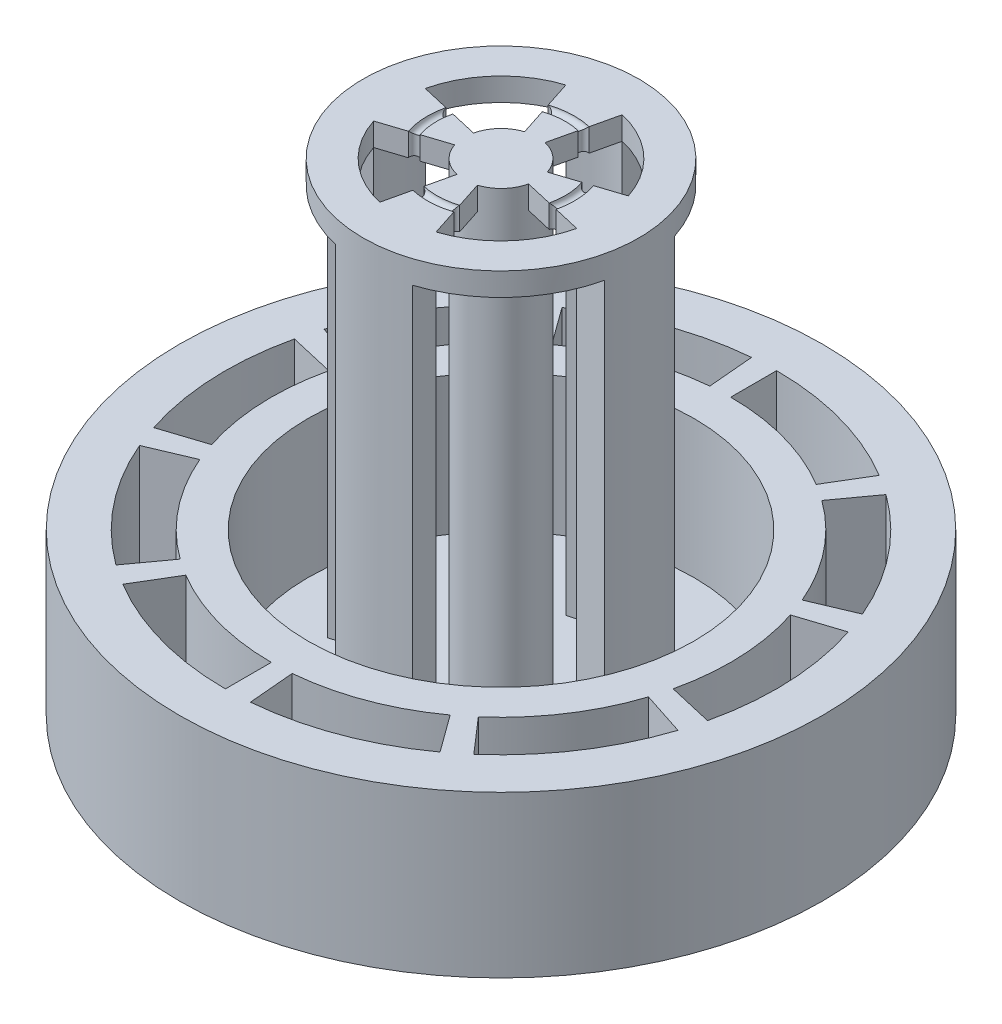
SolidWorks part; units mm, degrees
ref_plane "Front Plane" through (0, 0, 0) normal (0, 0, 1) x (1, 0, 0)
ref_plane "Top Plane" through (0, 0, 0) normal (0, 1, 0) x (1, 0, 0)
ref_plane "Right Plane" through (0, 0, 0) normal (1, 0, 0) x (0, 0, -1)
sketch "Sketch1" plane through (0, 0, 0) normal (0, 1, 0) x (1, 0, 0)
  circle A0 centre (0, 0) radius 70
extrude "Boss-Extrude1" add sketch "Sketch1" along normal blind 5
sketch "Sketch2" plane through (0, 0, 0) normal (0, 1, 0) x (1, 0, 0)
  line L0 (-17.6336, -24.2705) -> (-35.2671, -48.541)
  line L1 (-15.4511, -25.715) -> (-30.9023, -51.43)
  line L2 (-7.6085, -2.4721) -> (-57.0634, -18.541)
  line L3 (-27.6151, -11.7219) -> (-55.2303, -23.4439)
  line L4 (-28.5317, 9.2705) -> (-57.0634, 18.541)
  line L5 (-7.795, 1.7996) -> (-58.4622, 13.4971)
  line L6 (-17.6336, 24.2705) -> (-35.2671, 48.541)
  line L7 (-19.6818, 22.6413) -> (-39.3635, 45.2826)
  line L8 (0, 30) -> (0, 60)
  line L9 (-2.6147, 29.8858) -> (-5.2293, 59.7717)
  line L10 (17.6336, 24.2705) -> (35.2671, 48.541)
  line L11 (15.4511, 25.715) -> (30.9023, 51.43)
  line L12 (7.6085, 2.4721) -> (57.0634, 18.541)
  line L13 (27.6151, 11.7219) -> (55.2303, 23.4439)
  line L14 (28.5317, -9.2705) -> (57.0634, -18.541)
  line L15 (7.795, -1.7996) -> (58.4622, -13.4971)
  line L16 (17.6336, -24.2705) -> (35.2671, -48.541)
  line L17 (19.6818, -22.6413) -> (39.3635, -45.2826)
  line L18 (6.7485, 29.2311) -> (1.7996, 7.795)
  line L19 (-1.7996, -7.795) -> (-6.7485, -29.2311)
  line L20 (-9.2705, 28.5317) -> (-2.4721, 7.6085)
  line L22 (2.4721, -7.6085) -> (9.2705, -28.5317)
  line L25 (0, -30) -> (0, -60)
  line L27 (2.6147, -29.8858) -> (5.2293, -59.7717)
  circle A0 centre (0, 0) radius 50
  circle A1 centre (0, 0) radius 60
  circle A2 centre (0, 0) radius 42
  circle A3 centre (0, 0) radius 30
  circle A4 centre (0, 0) radius 22
  circle A5 centre (0, 0) radius 8
  circle A6 centre (0, 0) radius 70
  circle A7 centre (0, 0) radius 38
  point P51 (0, 0)
  point P52 (0, 0)
  point P64 (0, 0)
  dimension "D1" = 10
extrude "Boss-Extrude2" add sketch "Sketch2" along normal blind 35 contours A6 A1 | A2 L25 A0 L27 | A2 L27 A0 L16 | A2 L16 A0 L17 | A2 L17 A0 L14 | A2 L1 A0 L25 | A2 L0 A0 L1 | A2 L3 A0 L0 | A2 L2 A0 L3 | A2 L5 A0 L2 | A2 L4 A0 L5 | A2 L7 A0 L4 | A2 L6 A0 L7 | A2 L9 A0 L6 | A2 L8 A0 L9 | A2 L11 A0 L8 | A2 L10 A0 L11 | A2 L13 A0 L10 | A2 L14 A0 L15 | A2 L15 A0 L12 | A2 L12 A0 L13 | L25 A1 L27 A0 | L16 A1 L17 A0 | L14 A1 L15 A0 | L12 A1 L13 A0 | L10 A1 L11 A0 | L8 A1 L9 A0 | L6 A1 L7 A0 | L4 A1 L5 A0 | L2 A1 L3 A0 | L0 A1 L1 A0 region at (-25.445, 0, 38.4432) region at (-35.6521, 0, 28.359) region at (-30.4305, 0, 45.9755) region at (-43.1818, 0, 16.145) region at (-12.1742, 0, 43.8987) region at (-51.6425, 0, 19.3083) region at (-45.5121, 0, 1.9871) region at (2.0109, 0, 46.0574) region at (2.4049, 0, 55.0815) region at (-44.4246, 0, -12.32) region at (15.9539, 0, 42.6706) region at (-53.1288, 0, -14.7339) region at (-37.9881, 0, -25.1438) region at (28.6987, 0, 36.0793) region at (34.3217, 0, 43.1483) region at (-28.6987, 0, -36.0793) region at (37.9881, 0, 25.1438) region at (-34.3217, 0, -43.1483) region at (-15.9539, 0, -42.6706) region at (44.4246, 0, 12.32) region at (45.5121, 0, -1.9871) region at (53.1288, 0, 14.7339) region at (-2.0109, 0, -46.0574) region at (-2.4049, 0, -55.0815) region at (12.1742, 0, -43.8987) region at (25.445, 0, -38.4432) region at (43.1818, 0, -16.145) region at (30.4305, 0, -45.9755) region at (35.6521, 0, -28.359) region at (51.6425, 0, -19.3083) region at (-68.0201, 0, 0)
extrude "Boss-Extrude3" add sketch "Sketch2<10>" along normal blind 100 contours A4 L18 A3 L20 | A4 L15 A3 L12 | A4 L19 A3 L22 | A4 L5 A3 L2 | A5 region at (-25.862, 0, 1.1292) region at (1.1292, 0, 25.862) region at (0, 0, 0) region at (-1.1292, 0, -25.862) region at (25.862, 0, -1.1292)
sketch "Sketch2<10>" plane through (0, 0, 0) normal (0, 1, 0) x (1, 0, 0) same geometry as "Sketch2"
sketch "Sketch4" plane through (0, 100, 0) normal (0, 1, 0) x (1, 0, 0)
  line L0 (21.4361, -4.9489) -> (7.795, -1.7996)
  line L2 (2.4721, -7.6085) -> (6.7984, -20.9232)
  line L3 (20.9232, 6.7984) -> (7.6085, 2.4721)
  line L4 (-6.7984, 20.9232) -> (-2.4721, 7.6085)
  line L5 (-1.7996, -7.795) -> (-4.9489, -21.4361)
  line L6 (4.9489, 21.4361) -> (1.7996, 7.795)
  line L7 (-7.6085, -2.4721) -> (-20.9232, -6.7984)
  line L8 (-7.795, 1.7996) -> (-21.4361, 4.9489)
  arc A0 (7.6085, 2.4721) -> (1.7996, 7.795) centre (0, 0) ccw
  arc A1 (20.9232, 6.7984) -> (4.9489, 21.4361) centre (0, 0) ccw
  circle A2 centre (0, 0) radius 30
  arc A3 (6.7984, -20.9232) -> (21.4361, -4.9489) centre (0, 0) ccw
  arc A4 (2.4721, -7.6085) -> (7.795, -1.7996) centre (0, 0) ccw
  arc A5 (-7.6085, -2.4721) -> (-1.7996, -7.795) centre (0, 0) ccw
  arc A6 (-20.9232, -6.7984) -> (-4.9489, -21.4361) centre (0, 0) ccw
  arc A7 (-2.4721, 7.6085) -> (-7.795, 1.7996) centre (0, 0) ccw
  arc A8 (-6.7984, 20.9232) -> (-21.4361, 4.9489) centre (0, 0) ccw
extrude "Boss-Extrude4" add sketch "Sketch4" along normal blind 5
sketch "Sketch5" plane through (0, 105, 0) normal (0, 1, 0) x (1, 0, 0)
  line L0 (-15.5899, 3.5992) -> (-13.6412, 3.1493)
  line L1 (-15.2169, -4.9443) -> (-13.3148, -4.3262)
  line L2 (3.5992, 15.5899) -> (3.1493, 13.6412)
  line L3 (-4.9443, 15.2169) -> (-4.3262, 13.3148)
  line L4 (15.5899, -3.5992) -> (13.6412, -3.1493)
  line L5 (15.2169, 4.9443) -> (13.3148, 4.3262)
  line L6 (2.4721, -7.6085) -> (6.7984, -20.9232) construction
  line L7 (-4.9489, -21.4361) -> (-1.7996, -7.795) construction
  line L8 (-3.5992, -15.5899) -> (-3.1493, -13.6412)
  line L10 (4.9443, -15.2169) -> (4.3262, -13.3148)
  arc A0 (-13.3148, -4.3262) -> (-15.2169, -4.9443) centre (-14.2658, -4.6353) ccw
  arc A1 (-15.5899, 3.5992) -> (-13.6412, 3.1493) centre (-14.6156, 3.3743) ccw
  arc A2 (-4.3262, 13.3148) -> (-4.9443, 15.2169) centre (-4.6353, 14.2658) ccw
  arc A3 (3.5992, 15.5899) -> (3.1493, 13.6412) centre (3.3743, 14.6156) ccw
  arc A4 (13.3148, 4.3262) -> (15.2169, 4.9443) centre (14.2658, 4.6353) ccw
  arc A5 (15.5899, -3.5992) -> (13.6412, -3.1493) centre (14.6156, -3.3743) ccw
  arc A6 (4.3262, -13.3148) -> (4.9443, -15.2169) centre (4.6353, -14.2658) ccw
  arc A7 (-3.5992, -15.5899) -> (-3.1493, -13.6412) centre (-3.3743, -14.6156) ccw
  point P21 (0, 0)
extrude "Cut-Extrude2" cut sketch "Sketch5" against normal up to next
sketch "Sketch8" plane through (0, 0, 0) normal (0.9744, 0, 0.225) x (0.225, 0, -0.9744)
  line L0 (14, 105) -> (16, 105)
  line L1 (0, 65) -> (0, 60)
  arc A0 (14, 105) -> (16, 105) centre (15, 105) ccw
revolve "Cut-Revolve1" cut sketch "Sketch8" angle 360 about L1 region at (3.3743, 104.5756, -14.6156)
sketch "Sketch9" plane through (0, 105, 0) normal (0, 1, 0) x (1, 0, 0)
  line L0 (0, 0) -> (16.2201, -14.863)
  arc A0 (6.7984, -20.9232) -> (21.4361, -4.9489) centre (0, 0) ccw construction
